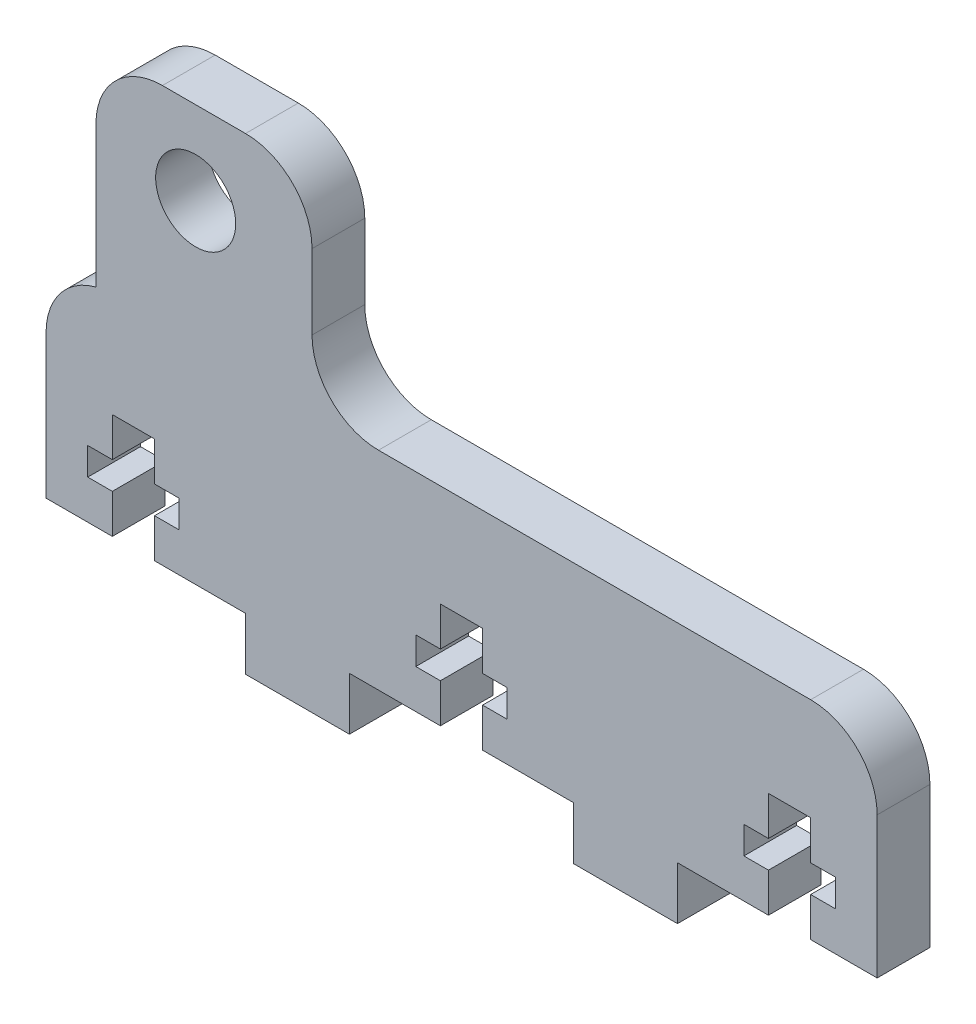
SolidWorks part; units mm, degrees
ref_plane "Front Plane" through (0, 0, 0) normal (0, 0, 1) x (1, 0, 0)
ref_plane "Top Plane" through (0, 0, 0) normal (0, 1, 0) x (1, 0, 0)
ref_plane "Right Plane" through (0, 0, 0) normal (1, 0, 0) x (0, 0, -1)
sketch "Sketch1" plane through (0, 0, 0) normal (0, 0, 1) x (1, 0, 0)
  line L0 (36.5, 0) -> (63.4742, 0)
  line L1 (0, 0) -> (24, 0)
  line L2 (0, 0) -> (0, 25)
  line L3 (6, 50) -> (32, 50)
  line L4 (100, 0) -> (100, 25)
  line L5 (75.9742, 0) -> (100, 0)
  line L6 (24, 0) -> (24, -6.35)
  line L7 (24, -6.35) -> (36.5, -6.35)
  line L8 (36.5, 0) -> (36.5, -6.35)
  line L10 (32, 50) -> (32, 25)
  line L11 (32, 25) -> (100, 25)
  line L12 (63.4742, 0) -> (63.4742, -6.35)
  line L13 (63.4742, -6.35) -> (75.9742, -6.35)
  line L14 (75.9742, 0) -> (75.9742, -6.35)
  line L18 (0, 25) -> (6, 25)
  line L19 (6, 50) -> (6, 25)
  dimension "D1" = 100
  dimension "D2" = 50
  dimension "D3" = 24
  dimension "D4" = 6.35
  dimension "D5" = 12.5
  dimension "D6" = 32
  dimension "D7" = 39.4742
  dimension "D8" = 6
extrude "Boss-Extrude1" add sketch "Sketch1" along normal blind 6.35
sketch "Sketch2" plane through (0, 0, 6.35) normal (0, 0, 1) x (1, 0, 0)
  line L0 (0, 0) -> (24, 0) construction
  line L1 (0, 25) -> (0, 0) construction
  circle A0 centre (18, 40) radius 4.815
  dimension "D1" = 9.63
  dimension "D2" = 40
  dimension "D3" = 18
extrude "Cut-Extrude1" cut sketch "Sketch2" against normal blind 6.35
sketch "Sketch3" plane through (0, 0, 6.35) normal (0, 0, 1) x (1, 0, 0)
  line L0 (7.9729, 0) -> (7.9729, 4.7)
  line L1 (7.9729, 12.7) -> (13.0529, 12.7)
  line L2 (13.0529, 0) -> (13.0529, 4.7)
  line L3 (7.9729, 8) -> (7.9729, 12.7)
  line L4 (5.0138, 8) -> (7.9729, 8)
  line L5 (5.0138, 8) -> (5.0138, 4.7)
  line L6 (5.0138, 4.7) -> (7.9729, 4.7)
  line L7 (16.012, 8) -> (16.012, 4.7)
  line L8 (13.0529, 8) -> (16.012, 8)
  line L9 (13.0529, 8) -> (13.0529, 12.7)
  line L10 (13.0529, 4.7) -> (16.012, 4.7)
  line L11 (13.0529, 0) -> (7.9729, 0)
  line L12 (10.5129, 12.7) -> (10.5129, 0) construction
  line L13 (0, 0) -> (24, 0) construction
  line L14 (24, -6.35) -> (36.5, -6.35) construction
  line L15 (47.4471, 12.7) -> (52.5271, 12.7)
  line L16 (47.4471, 8) -> (47.4471, 12.7)
  line L17 (52.5271, 8) -> (52.5271, 12.7)
  line L18 (49.9871, 12.7) -> (49.9871, 0) construction
  line L19 (52.5271, 4.7) -> (55.4862, 4.7)
  line L20 (52.5271, 8) -> (55.4862, 8)
  line L21 (55.4862, 8) -> (55.4862, 4.7)
  line L22 (52.5271, 0) -> (52.5271, 4.7)
  line L23 (52.5271, 0) -> (47.4471, 0)
  line L24 (47.4471, 0) -> (47.4471, 4.7)
  line L25 (44.488, 4.7) -> (47.4471, 4.7)
  line L26 (44.488, 8) -> (44.488, 4.7)
  line L27 (44.488, 8) -> (47.4471, 8)
  line L28 (86.9213, 12.7) -> (92.0013, 12.7)
  line L29 (86.9213, 8) -> (86.9213, 12.7)
  line L30 (92.0013, 8) -> (92.0013, 12.7)
  line L31 (89.4613, 12.7) -> (89.4613, 0) construction
  line L32 (92.0013, 4.7) -> (94.9604, 4.7)
  line L33 (92.0013, 8) -> (94.9604, 8)
  line L34 (94.9604, 8) -> (94.9604, 4.7)
  line L35 (92.0013, 0) -> (92.0013, 4.7)
  line L36 (92.0013, 0) -> (86.9213, 0)
  line L37 (86.9213, 0) -> (86.9213, 4.7)
  line L38 (83.9622, 4.7) -> (86.9213, 4.7)
  line L39 (83.9622, 8) -> (83.9622, 4.7)
  line L40 (83.9622, 8) -> (86.9213, 8)
  line L41 (36.5, 0) -> (63.4742, 0) construction
  point P17 (30.25, -6.35)
  dimension "D1" = 12.7
  dimension "D2" = 10.9982
  dimension "D3" = 5.4991
  dimension "D4" = 3.3
  dimension "D5" = 19.7371
  dimension "D6" = 5.08
  dimension "D7" = 3
  dimension "D8" = 39.4742
extrude "Cut-Extrude2" cut sketch "Sketch3" against normal through all
fillet "Fillet1" radius 8 5 edges at (100, 25, 3.175) (32, 25, 3.175) (32, 50, 3.175) (6, 50, 3.175) (0, 25, 3.175)
